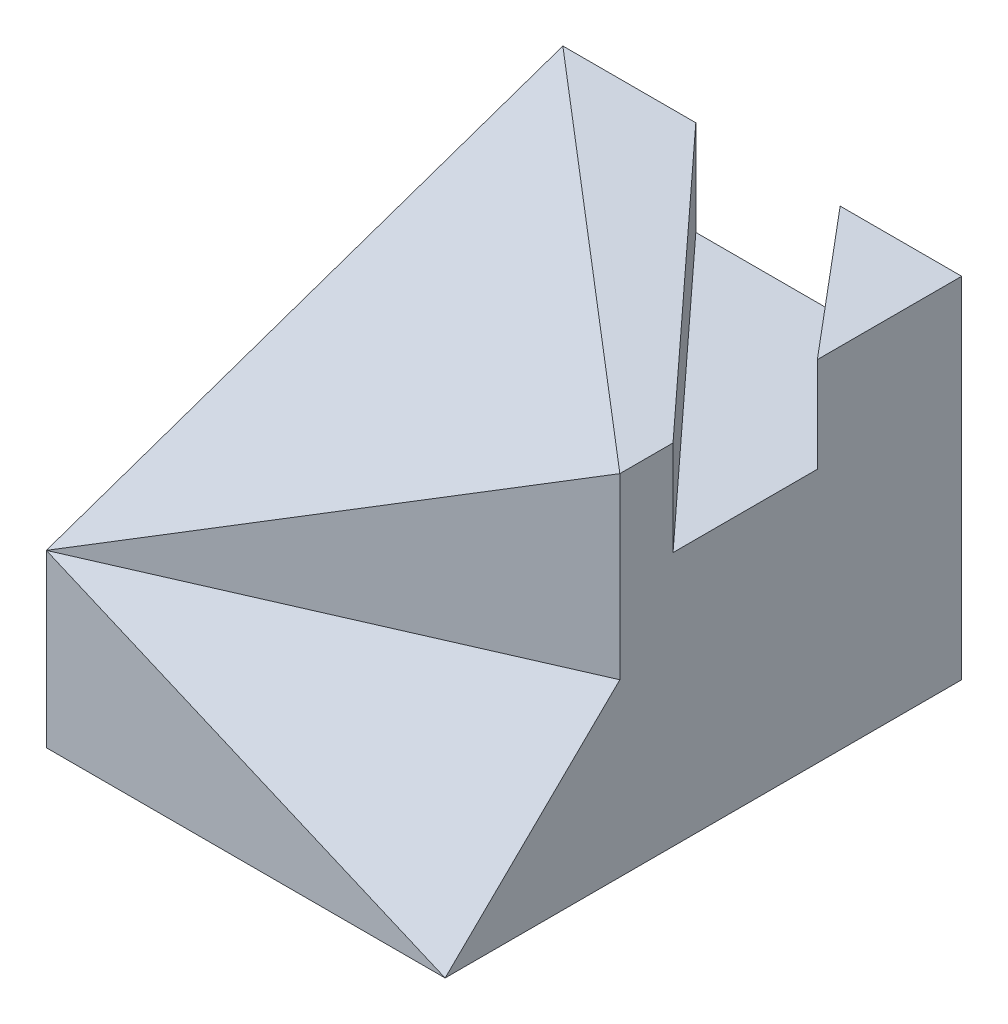
SolidWorks part; units mm, degrees
ref_plane "Front Plane" through (0, 0, 0) normal (0, 0, 1) x (1, 0, 0)
ref_plane "Top Plane" through (0, 0, 0) normal (0, 1, 0) x (1, 0, 0)
ref_plane "Right Plane" through (0, 0, 0) normal (1, 0, 0) x (0, 0, -1)
sketch "Sketch1" plane through (0, 0, 0) normal (0, 1, 0) x (1, 0, 0)
  line L1 (-26.25, -34) -> (26.25, -34)
  line L2 (-26.25, -34) -> (-26.25, 34)
  line L3 (-26.25, 34) -> (26.25, 34)
  line L4 (26.25, -34) -> (26.25, 34)
  line L5 (-26.25, -34) -> (26.25, 34) construction
  line L6 (-26.25, 34) -> (26.25, -34) construction
  point P0 (0, 0)
  dimension "D1" = 52.5
  dimension "D2" = 68
extrude "Boss-Extrude1" add sketch "Sketch1" along normal blind 46
sketch "Sketch2" plane through (0, 46, 0) normal (0, 1, 0) x (1, 0, 0)
  line L0 (10.25, 34) -> (26.25, 15)
  line L1 (-8.75, 34) -> (26.25, -4)
  line L2 (-26.25, 34) -> (26.25, -11)
  line L3 (26.25, -11) -> (-26.25, -34)
  line L4 (26.25, -34) -> (26.25, 34)
  line L5 (26.25, 34) -> (-26.25, 34)
  line L6 (-26.25, 34) -> (-26.25, -34)
  line L7 (-26.25, -34) -> (26.25, -34)
  line L8 (26.25, -34) -> (26.25, 34)
  line L9 (26.25, 34) -> (-26.25, 34)
  line L10 (-26.25, 34) -> (-26.25, -34)
  line L11 (-26.25, -34) -> (26.25, -34)
  line M5 (26.25, -34) -> (26.25, 34)
  line M6 (26.25, 34) -> (-26.25, 34)
  line M8 (-26.25, -34) -> (26.25, -34)
  dimension "D2" = 16
  dimension "D3" = 19
  dimension "D4" = 19
  dimension "D5" = 19
  dimension "D6" = 23
  dimension "D1" = 0
extrude "Cut-Extrude1" cut sketch "Sketch2" against normal blind 12.5 contours L1 L0 M6 M5 region at (12.7068, 46, -19.4568)
extrude "Cut-Extrude2" cut sketch "Sketch2<3>" against normal blind 23.5 contours L3 M5 M8 region at (8.75, 46, 26.3333)
sketch "Sketch2<3>" plane through (0, 46, 0) normal (0, 1, 0) x (1, 0, 0) same geometry as "Sketch2"
ref_plane "Plane1" through (8.9113, 20.793, 20.341) normal (0.2929, 0.6835, 0.6686) x (0.9561, -0.2094, -0.2048)
sketch "Sketch3" plane through (8.9113, 20.793, 20.341) normal (0.2929, 0.6835, 0.6686) x (0.9561, -0.2094, -0.2048)
  line L0 (18.1341, 7.8709) -> (-36.7743, -8.5702) construction
  line L1 (18.1341, 7.8709) -> (-36.7743, -8.5702)
  line L2 (18.1341, 7.8709) -> (18.1341, -24.3044)
  line L3 (-36.7743, -8.5702) -> (18.1341, -24.3044)
extrude "Cut-Extrude3" cut sketch "Sketch3" along normal up to next
ref_plane "Plane2" through (-10.3123, 34.8132, 12.031) normal (0.2696, -0.9102, -0.3145) x (-0.963, -0.2548, -0.0881)
sketch "Sketch4" plane through (-10.3123, 34.8132, 12.031) normal (0.2696, -0.9102, -0.3145) x (-0.963, -0.2548, -0.0881)
  line L0 (16.5505, 47.1603) -> (-37.9682, 4.6285)
  line L1 (16.5505, 47.1603) -> (16.5505, -24.7859)
  line L2 (16.5505, -24.7859) -> (-37.9682, 4.6285)
extrude "Cut-Extrude4" cut sketch "Sketch4" against normal up to next
